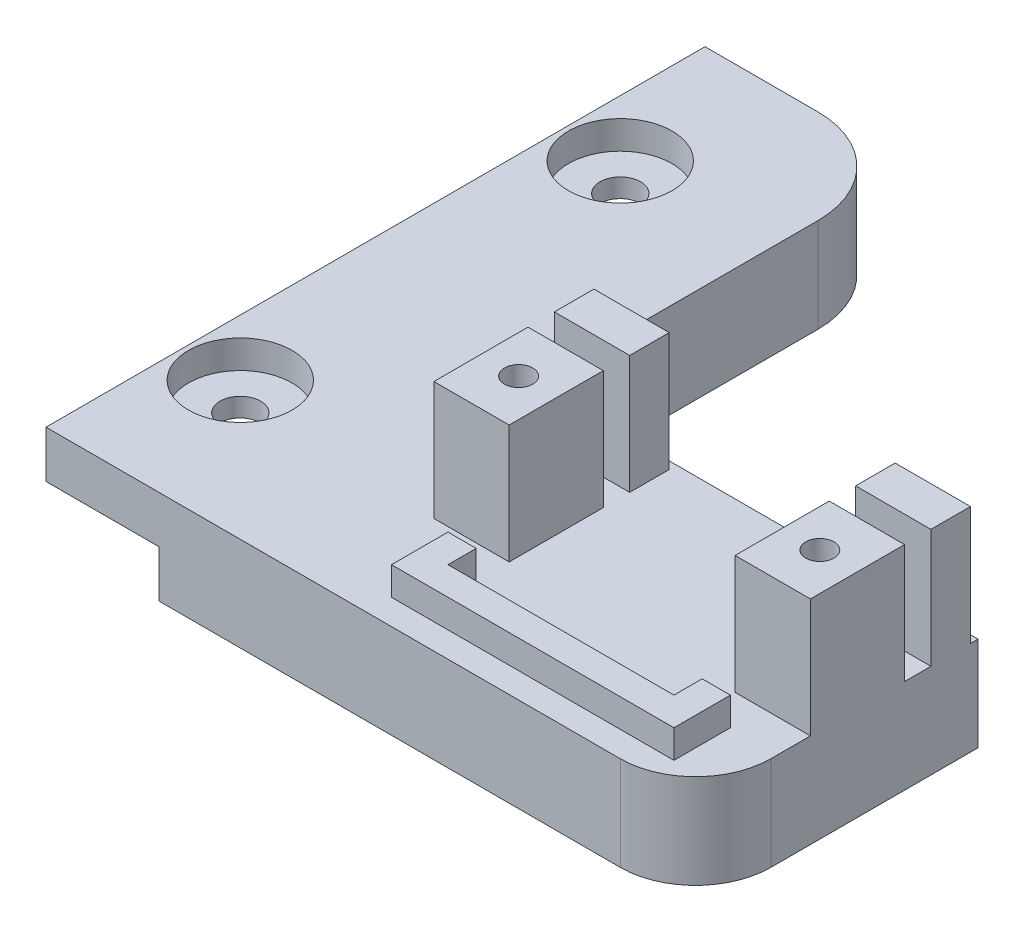
SolidWorks part; units mm, degrees
material "ABS"
ref_plane "Front Plane" through (0, 0, 0) normal (0, 0, 1) x (1, 0, 0)
ref_plane "Top Plane" through (0, 0, 0) normal (0, 1, 0) x (1, 0, 0)
ref_plane "Right Plane" through (0, 0, 0) normal (1, 0, 0) x (0, 0, -1)
sketch "Sketch1" plane through (0, 0, 0) normal (0, 1, 0) x (1, 0, 0)
  line L0 (0, 0) -> (-10, 0) construction
  line L1 (-10, 35) -> (0, 35)
  line L2 (-10, 35) -> (-10, -35)
  line L3 (-10, -35) -> (0, -35)
  line L4 (0, 35) -> (0, -35)
  line L6 (0, -35) -> (47, -35)
  line L7 (0, -35) -> (0, -5)
  line L8 (0, -5) -> (47, -5)
  line L9 (47, -35) -> (47, -5)
  dimension "D1" = 70
  dimension "D2" = 10
  dimension "D3" = 47
  dimension "D4" = 30
extrude "Boss-Structure" add sketch "Sketch1" against normal blind 10 contours L0 L4 L1 L2 | L4 L0 L2 L3 | L6 L9 L8 L4 region at (-5, 0, 17.5) region at (-5, 0, -17.5) region at (23.5, 0, 20)
sketch "Sketch2" plane through (-10, 0, 0) normal (-1, 0, 0) x (0, 0, 1)
  line L0 (35, -10) -> (35, 0) construction
  line L1 (-35, 0) -> (35, 0)
  line L2 (-35, 0) -> (-35, -5)
  line L3 (-35, -5) -> (35, -5)
  line L4 (35, 0) -> (35, -5)
extrude "Boss-Attache" add sketch "Sketch2" along normal blind 12
sketch "Servo" plane through (0, 0, 0) normal (0, 1, 0) x (1, 0, 0)
  line L1 (47, -35) -> (47, -5) construction
  line L2 (15, -5.8) -> (39, -5.8)
  line L3 (15, -5.8) -> (15, -29.3)
  line L4 (15, -29.3) -> (39, -29.3)
  line L5 (39, -5.8) -> (39, -29.3)
  line L6 (27, -29.3) -> (27, -5.8) construction
  line L7 (15, -12.8) -> (7, -12.8)
  line L8 (15, -12.8) -> (15, -10)
  line L9 (15, -10) -> (7, -10)
  line L10 (7, -12.8) -> (7, -10)
  line L11 (15, -26.3) -> (12, -26.3)
  line L12 (15, -5.8) -> (7, -5.8)
  line L13 (15, -5.8) -> (15, -10)
  line L14 (15, -10) -> (7, -10)
  line L15 (7, -5.8) -> (7, -10)
  line L16 (7, -12.8) -> (15, -12.8)
  line L17 (7, -12.8) -> (7, -22.8)
  line L18 (7, -22.8) -> (15, -22.8)
  line L19 (15, -12.8) -> (15, -22.8)
  line L20 (12, -26.3) -> (12, -32.3)
  line L21 (12, -32.3) -> (42, -32.3)
  line L22 (27, -32.3) -> (27, -29.3)
  line L23 (42, -26.3) -> (42, -32.3)
  line L24 (39, -26.3) -> (42, -26.3)
  line L25 (47, -22.8) -> (39, -22.8)
  line L26 (39, -12.8) -> (39, -22.8)
  line L27 (47, -12.8) -> (39, -12.8)
  line L28 (47, -12.8) -> (47, -22.8)
  line L29 (39, -10) -> (47, -10)
  line L30 (47, -12.8) -> (47, -10)
  line L31 (39, -12.8) -> (47, -12.8)
  line L32 (39, -12.8) -> (39, -10)
  line L33 (39, -10) -> (47, -10)
  line L34 (47, -5.8) -> (47, -10)
  line L35 (39, -5.8) -> (47, -5.8)
  line L36 (39, -5.8) -> (39, -10)
  line L37 (-22, 0) -> (52.8948, 0) construction
  line L38 (-22, -35) -> (-22, 35) construction
  line L39 (27, 0) -> (27, -1.5) construction
  line L40 (27, -5.8) -> (27, -1.5) construction
  dimension "D1" = 24
  dimension "D2" = 23.5
  dimension "D3" = 4.3
  dimension "D4" = 8
  dimension "D5" = 2.8
  dimension "D6" = 4.2
  dimension "D7" = 8
  dimension "D8" = 10
  dimension "D9" = 3
  dimension "D10" = 6
  dimension "D11" = 1.5
extrude "Boss-Servo_1" add sketch "Servo" along normal blind 12.6 contours L12 L15 L9 L3 | L17 L18 L3 L7 | L28 L27 L5 L25 | L35 L5 L29 L34 region at (11, 0, 7.9) region at (43, 0, 7.9) region at (11, 0, 17.8) region at (43, 0, 17.8)
extrude "Boss-Servo_2" add sketch "Sketch3<3>" along normal blind 3 contours L21 L22 L4 L3 L11 L20 | L24 L5 L4 L22 L21 L23 region at (18.5, 0, 30.3) region at (35.5, 0, 30.3)
sketch "Sketch3<3>" plane through (0, 0, 0) normal (0, 1, 0) x (1, 0, 0) same geometry as "Servo"
fillet "Fillet1" radius 10 1 edges at (0, -5, -35)
fillet "Fillet2" radius 8 1 edges at (47, -5, 35)
sketch "Sketch4" plane through (0, 12.6, 0) normal (0, 1, 0) x (1, 0, 0)
  line L0 (11, -17.8) -> (7, -17.8) construction
  line L1 (7, -12.8) -> (7, -22.8) construction
  line L3 (11, -12.8) -> (11, -17.8) construction
  line L4 (15, -12.8) -> (7, -12.8) construction
  line L5 (43, -12.8) -> (43, -17.8) construction
  line L6 (47, -12.8) -> (39, -12.8) construction
  line L7 (9.5, -17.8) -> (12.5, -17.8) construction
  line L8 (41.5, -17.8) -> (44.5, -17.8) construction
  circle A0 centre (11, -17.8) radius 1.5
  circle A1 centre (43, -17.8) radius 1.5
  dimension "D1" = 3
extrude "Cut-Extrude1" cut sketch "Sketch4" against normal blind 6
sketch "Sketch5" plane through (0, 0, 0) normal (0, 1, 0) x (1, 0, 0)
  line L0 (-16, 35) -> (-16, 20) construction
  line L1 (-22, 35) -> (-10, 35) construction
  line L2 (-16, -35.3614) -> (-16, -20.3614) construction
  dimension "D1" = 6
  dimension "D2" = 15
hole_wizard "CBORE for #6 Pan Head Machine Screw1" positions "Sketch6" profile "Sketch7" counterbore size "#6" standard "ANSI Inch" end condition up to next
sketch "Sketch6" plane through (0, 0, 0) normal (0, 1, 0) x (1, 0, 0)
  point P0 (-16, 20)
  point P3 (-16, -20.3614)
sketch "Sketch7" plane through (-16, 0, -20) normal (1, 0, 0) x (0, 0, 1)
  line L0 (0, 0) -> (0, 5)
  line L1 (0, 5) -> (2.1526, 5)
  line L3 (2.1526, 5) -> (2.1526, 3)
  line L4 (2.1526, 3) -> (5.5, 3)
  line L5 (5.5, 3) -> (5.5, 0)
  line L7 (5.5, 0) -> (0, 0)
  line L11 (0, -6.35) -> (0, 107.95) construction
  dimension "Thru Hole Dia." = 4.3053
  dimension "Thru Hole Depth" = 5
  dimension "C'Bore Dia." = 11
  dimension "C'Bore Depth" = 3
